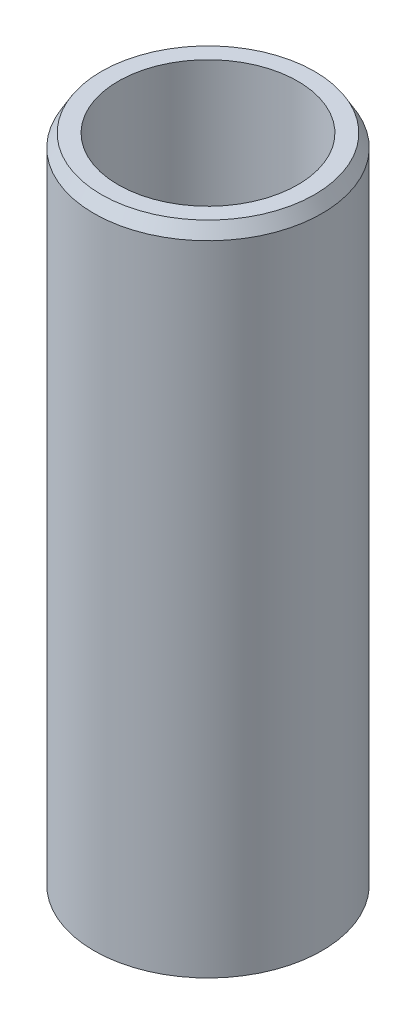
SolidWorks part; units mm, degrees
ref_plane "Front Plane" through (0, 0, 0) normal (0, 0, 1) x (1, 0, 0)
ref_plane "Top Plane" through (0, 0, 0) normal (0, 1, 0) x (1, 0, 0)
ref_plane "Right Plane" through (0, 0, 0) normal (1, 0, 0) x (0, 0, -1)
sketch "Sketch1" plane through (0, 0, 0) normal (0, 1, 0) x (1, 0, 0)
  circle A0 centre (0, 0) radius 50
  dimension "SHAFT_OD" = 100
extrude "Boss-Extrude1" add sketch "Sketch1" along normal blind 288.7452
sketch "Sketch2" plane through (0, 0, 0) normal (0, 1, 0) x (1, 0, 0)
  circle A0 centre (0, 0) radius 39.3678
  dimension "BORE_D" = 78.7357
extrude "Cut-Extrude1" cut sketch "Sketch2" along normal through all
chamfer "Chamfer1" distance 5.5778 angle 30 2 edges at (0, 288.7452, 50) (0, 0, 50) first distance on face at (0, 288.7452, 50) first distance on face at (0, 0, 39.3678)
